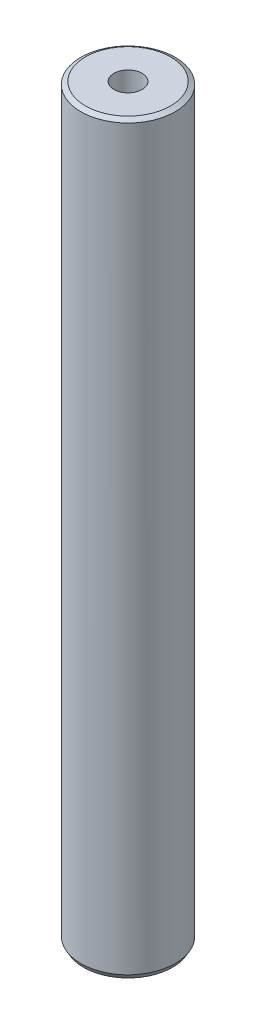
SolidWorks part; units mm, degrees
ref_plane "Front Plane" through (0, 0, 0) normal (0, 0, 1) x (1, 0, 0)
ref_plane "Top Plane" through (0, 0, 0) normal (0, 1, 0) x (1, 0, 0)
ref_plane "Right Plane" through (0, 0, 0) normal (1, 0, 0) x (0, 0, -1)
sketch "Sketch1" plane through (0, 0, 0) normal (0, 1, 0) x (1, 0, 0)
  circle A0 centre (0, 0) radius 37.5
  dimension "SHAFT_OD" = 75
extrude "Boss-Extrude1" add sketch "Sketch1" along normal blind 591.9387
sketch "Sketch2" plane through (0, 0, 0) normal (0, 1, 0) x (1, 0, 0)
  circle A0 centre (0, 0) radius 11.1779
  dimension "BORE_D" = 22.3559
extrude "Cut-Extrude1" cut sketch "Sketch2" along normal through all
chamfer "Chamfer1" distance 2.1267 angle 60.112 2 edges at (0, 591.9387, 37.5) (0, 0, 37.5) first distance on face at (0, 591.9387, 37.5) first distance on face at (0, 0, 11.1779)
